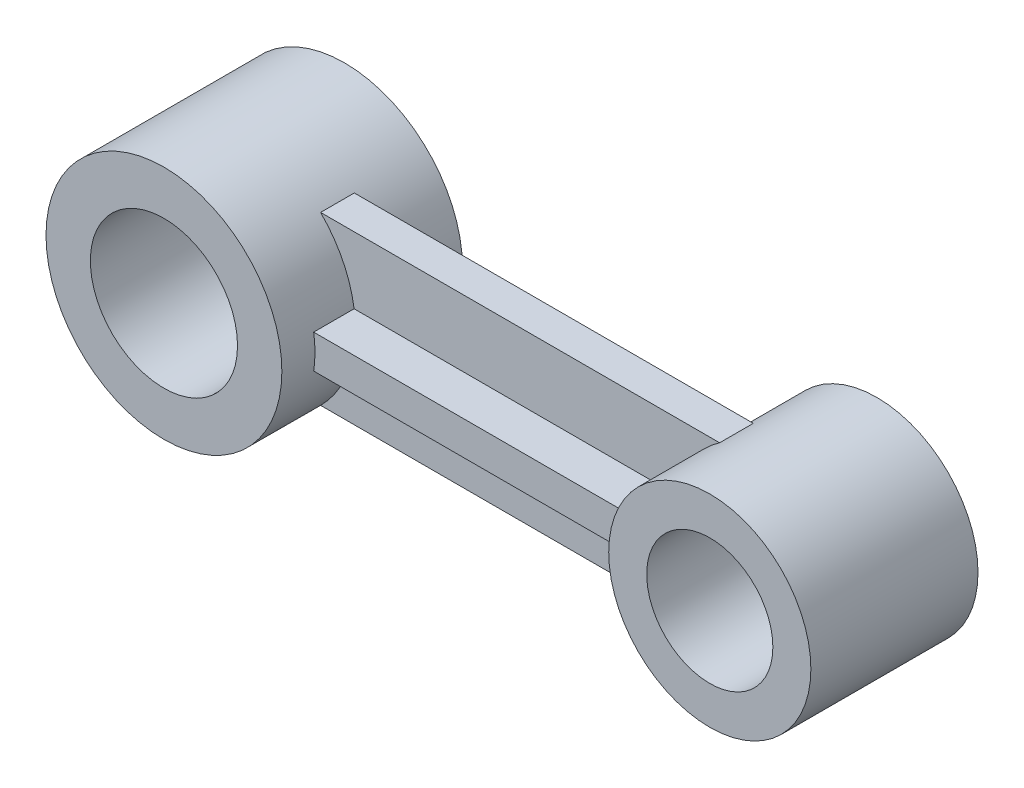
SolidWorks part; units mm, degrees
ref_plane "Front Plane" through (0, 0, 0) normal (0, 0, 1) x (1, 0, 0)
ref_plane "Top Plane" through (0, 0, 0) normal (0, 1, 0) x (1, 0, 0)
ref_plane "Right Plane" through (0, 0, 0) normal (1, 0, 0) x (0, 0, -1)
sketch "Sketch1" plane through (0, 0, 0) normal (0, 0, 1) x (1, 0, 0)
  line L0 (-73.7337, 0) -> (67.8858, 0) construction
  line L1 (-50.8, -27.2653) -> (-50.8, 25.4789) construction
  line L2 (-35.1172, 15.748) -> (40.0807, 15.748)
  line L4 (-35.1172, -15.748) -> (40.0807, -15.748)
  line L6 (-50.8, 15.748) -> (50.8, -15.748) construction
  line L7 (-50.8, -15.748) -> (50.8, 15.748) construction
  line L12 (-10.2419, 3.175) -> (10.2419, -3.175) construction
  line L13 (-10.2419, -3.175) -> (10.2419, 3.175) construction
  line L14 (50.8, 25.4789) -> (50.8, -25.4357) construction
  circle A0 centre (-50.8, 0) radius 13.8684
  circle A1 centre (-50.8, 0) radius 22.225
  circle A2 centre (50.8, 0) radius 11.8872
  circle A3 centre (50.8, 0) radius 19.05
  point P3 (0, 0)
  point P8 (0, 0)
  dimension "D4" = 27.7368
  dimension "D5" = 44.45
  dimension "D6" = 23.7744
  dimension "D7" = 38.1
  dimension "D1" = 101.6
  dimension "D2" = 31.496
extrude "Boss-Extrude1" add sketch "Sketch1" along normal mid plane 34.036 contours A1 A0 region at (-30.8561, 8.2853, 0)
extrude "Boss-Extrude2" add sketch "Sketch1<3>" along normal mid plane 31.496 separate body contours A3 A2 region at (59.4559, 16.3627, 0)
sketch "Sketch1<3>" plane through (0, 0, 0) normal (0, 0, 1) x (1, 0, 0) same geometry as "Sketch1"
extrude "Boss-Extrude3" add sketch "Sketch1<4>" along normal mid plane 6.35 contours A3 L2 A1 L4 region at (1.8247, 0, 0)
sketch "Sketch1<4>" plane through (0, 0, 0) normal (0, 0, 1) x (1, 0, 0) same geometry as "Sketch1"
sketch "Sketch3" plane through (0, 0, 0) normal (0, 0, 1) x (1, 0, 0)
  line L1 (-34.3299, 3.175) -> (34.3299, 3.175)
  line L2 (-34.3299, 3.175) -> (-34.3299, -3.175)
  line L3 (-34.3299, -3.175) -> (34.3299, -3.175)
  line L4 (34.3299, 3.175) -> (34.3299, -3.175)
  line L5 (-34.3299, 3.175) -> (34.3299, -3.175) construction
  line L6 (-34.3299, -3.175) -> (34.3299, 3.175) construction
  point P0 (0, 0)
  dimension "D1" = 6.35
extrude "Boss-Extrude5" add sketch "Sketch3" along normal mid plane 21.59
